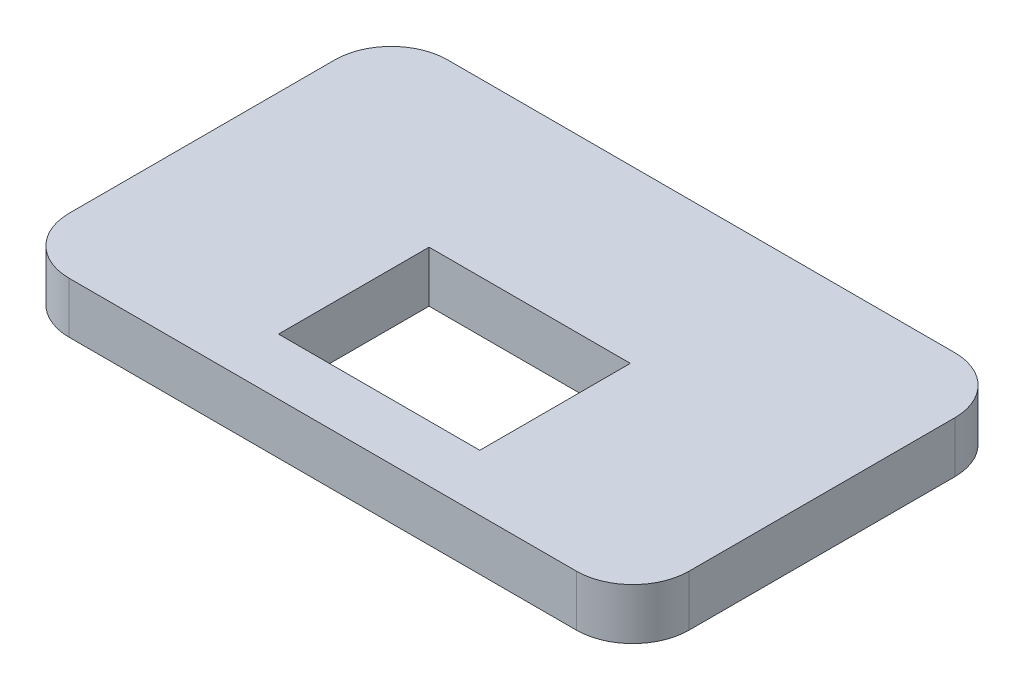
SolidWorks part; units mm, degrees
ref_plane "Front Plane" through (0, 0, 0) normal (0, 0, 1) x (1, 0, 0)
ref_plane "Top Plane" through (0, 0, 0) normal (0, 1, 0) x (1, 0, 0)
ref_plane "Right Plane" through (0, 0, 0) normal (1, 0, 0) x (0, 0, -1)
sketch "Sketch1" plane through (0, 0, 0) normal (0, 1, 0) x (1, 0, 0)
  line L1 (7, 0) -> (70, 0)
  line L2 (0, 7) -> (0, 40)
  line L3 (7, 47) -> (70, 47)
  line L4 (77, 7) -> (77, 40)
  arc A0 (7, 0) -> (0, 7) centre (7, 7) cw
  arc A1 (70, 0) -> (77, 7) centre (70, 7) ccw
  arc A2 (70, 47) -> (77, 40) centre (70, 40) cw
  arc A3 (0, 40) -> (7, 47) centre (7, 40) cw
  point P7 (0, 0)
  point P10 (77, 0)
  point P13 (77, 47)
  point P16 (0, 47)
  dimension "D3" = 7
  dimension "D1" = 77
  dimension "D2" = 47
extrude "Boss-Extrude1" add sketch "Sketch1" along normal blind 6.35
sketch "Sketch2" plane through (0, 6.35, 0) normal (0, 1, 0) x (1, 0, 0)
  line L0 (38.5, 47) -> (38.5, 0) construction
  line L1 (70, 47) -> (7, 47) construction
  line L2 (7, 0) -> (70, 0) construction
  line L3 (38.5, 25.7) -> (38.5, 7) construction
  line L4 (26, 25.7) -> (51, 25.7)
  line L5 (26, 25.7) -> (26, 7)
  line L6 (26, 7) -> (51, 7)
  line L7 (51, 25.7) -> (51, 7)
  dimension "D1" = 25
  dimension "D2" = 18.7
  dimension "D3" = 7
extrude "Cut-Extrude1" cut sketch "Sketch2" against normal through all
sketch "Sketch3" plane through (0, 6.35, 0) normal (0, 1, 0) x (1, 0, 0)
  line L0 (0, 30.9404) -> (77, 30.9404) construction
  line L3 (0, 40) -> (0, 7) construction
  line L4 (77, 7) -> (77, 40) construction
  text T0 "Score:" font "Century Gothic" height in points 16
